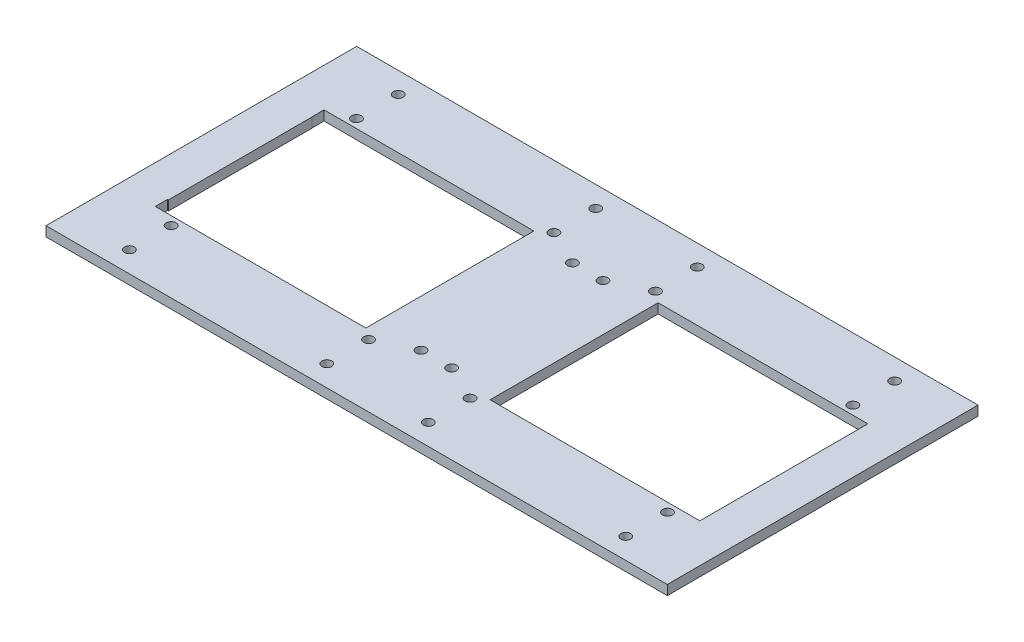
SolidWorks part; units mm, degrees
ref_plane "Front" through (0, 0, 0) normal (0, 0, 1) x (1, 0, 0)
ref_plane "Top" through (0, 0, 0) normal (0, 1, 0) x (1, 0, 0)
ref_plane "Right" through (0, 0, 0) normal (1, 0, 0) x (0, 0, -1)
sketch "Sketch1" plane through (0, 0, 0) normal (0, 1, 0) x (1, 0, 0)
  line L0 (0, -50.8) -> (203.2, -50.8)
  line L1 (0, 0) -> (203.2, 0)
  line L2 (0, 0) -> (0, -101.6)
  line L3 (0, -101.6) -> (203.2, -101.6)
  line L4 (203.2, 0) -> (203.2, -101.6)
  line L5 (101.6, 0) -> (0, 0)
  line L6 (50.8, 0) -> (50.8, -101.6)
  line L7 (101.6, 0) -> (203.2, 0)
  line L8 (152.4, 0) -> (152.4, -101.6)
  line L9 (12.7, -27.3231) -> (12.7, -74.2769)
  line L10 (81.28, -27.3231) -> (81.28, -74.2769)
  line L11 (12.7, -27.3231) -> (81.28, -27.3231)
  line L12 (12.7, -74.2769) -> (81.28, -74.2769)
  line L14 (121.92, -27.3231) -> (121.92, -74.2769)
  line L15 (101.6, 0) -> (101.6, -101.6)
  line L16 (12.7, 0) -> (12.7, -13.6616)
  line L17 (12.7, -13.6616) -> (12.7, -27.3231)
  line L18 (12.7, -74.2769) -> (12.7, -87.9384)
  line L19 (12.7, -87.9384) -> (12.7, -101.6)
  line L20 (190.5, -27.3231) -> (121.92, -27.3231)
  line L22 (190.5, -74.2769) -> (121.92, -74.2769)
  line L23 (190.5, -27.3231) -> (121.92, -27.3231)
  line L24 (106.6, -26.05) -> (96.6, -26.05)
  line L25 (106.6, -26.05) -> (106.6, -75.55)
  line L26 (106.6, -75.55) -> (96.6, -75.55)
  line L27 (96.6, -26.05) -> (96.6, -75.55)
  line L28 (106.6, -26.05) -> (96.6, -75.55) construction
  line L29 (106.6, -75.55) -> (96.6, -26.05) construction
  line L31 (121.92, -27.3231) -> (121.92, -23.3231)
  line L32 (190.5, -23.3231) -> (121.92, -23.3231)
  line L33 (190.5, -74.2769) -> (121.92, -74.2769)
  line L34 (190.5, -74.2769) -> (190.5, -78.2769)
  line L35 (121.92, -74.2769) -> (121.92, -78.2769)
  line L36 (190.5, -78.2769) -> (121.92, -78.2769)
  line L37 (81.28, -74.2769) -> (81.28, -78.2769)
  line L38 (81.28, -74.2769) -> (12.4051, -74.2769)
  line L39 (81.28, -78.2769) -> (12.4051, -78.2769)
  line L40 (12.4051, -74.2769) -> (12.4051, -78.2769)
  line L41 (81.28, -27.3231) -> (81.28, -23.3231)
  line L42 (81.28, -27.3231) -> (12.6484, -27.3231)
  line L43 (81.28, -23.3231) -> (12.6484, -23.3231)
  line L44 (12.6484, -27.3231) -> (12.6484, -23.3231)
  line L45 (118.2, -6.8308) -> (118.2, -20.4924)
  line L46 (190.5, -23.3231) -> (190.5, -27.3231)
  line L47 (190.5, -74.2769) -> (190.5, -27.3231)
  circle A0 centre (12.7, -6.8308) radius 1.6
  circle A1 centre (12.7, -81.1076) radius 1.6
  circle A2 centre (12.7, -94.7692) radius 1.6
  circle A3 centre (12.7, -20.4924) radius 1.6
  circle A4 centre (190.5, -94.7692) radius 1.6
  circle A5 centre (190.5, -81.1076) radius 1.6
  circle A6 centre (190.5, -6.8308) radius 1.6
  circle A7 centre (190.5, -20.4924) radius 1.6
  circle A8 centre (118.2, -6.8308) radius 1.6
  circle A10 centre (118.2, -94.7692) radius 1.6
  circle A12 centre (85, -94.7692) radius 1.6
  circle A15 centre (85, -6.8308) radius 1.6
  circle A16 centre (106.6, -26.05) radius 1.6
  circle A17 centre (96.6, -26.05) radius 1.6
  circle A18 centre (106.6, -75.55) radius 1.6
  circle A19 centre (96.6, -75.55) radius 1.6
  circle A20 centre (118.2, -20.4924) radius 1.6
  circle A21 centre (118.2, -81.1076) radius 1.6
  circle A22 centre (85, -81.1076) radius 1.6
  circle A23 centre (85, -20.4924) radius 1.6
  circle A24 centre (182.769, -6.8308) radius 1.6
  circle A25 centre (182.769, -20.4924) radius 1.6
  circle A26 centre (182.769, -94.7692) radius 1.6
  circle A27 centre (182.769, -81.1076) radius 1.6
  circle A28 centre (20.431, -94.7692) radius 1.6
  circle A29 centre (20.431, -81.1076) radius 1.6
  circle A30 centre (20.431, -20.4924) radius 1.6
  circle A31 centre (20.431, -6.8308) radius 1.6
  point P15 (12.7, -50.8)
  point P16 (12.7, -50.8)
  point P19 (81.28, -50.8)
  point P60 (101.6, -50.8)
  dimension "D5" = 10
  dimension "D7" = 46.9537
  dimension "D1" = 101.6
  dimension "D2" = 203.2
  dimension "D3" = 30.48
  dimension "D4" = 38.1
  dimension "D6" = 49.5
  dimension "D8" = 4
  dimension "D9" = 4
  dimension "D10" = 85
extrude "Boss-Extrude1" add sketch "Sketch1" against normal blind 3.175 contours A3 L17 L11 L6 L5 L16 A0 | A3 L17 L16 A0 L1 L2 L0 L9 | A2 L19 L18 A1 L9 L0 L2 L3 | A2 L19 L3 L6 L12 L18 A1 | L15 L0 L10 L12 L6 L3 | L15 L5 L6 L11 L10 L0 | L20 L8 L1 L15 L0 L14 | L8 L22 L14 L0 L15 L3 | L20 L0 L4 L7 L8 A6 A7 | L22 L8 L3 L4 L0 A4 A5 | A17 L27 L0 L15 L24 | A16 L24 L15 L0 L25 | A19 L26 L15 L0 L27 | A18 L25 L0 L15 L26 | A4 | A6 | A7 | A5 | A2 | A1 | A0 | A3 region at (6.2763, 0, 25.5482) region at (6.2668, 0, 76.0514) region at (32.1315, 0, 11.6058) region at (32.1315, 0, 89.9942) region at (79.5882, 0, 18.393) region at (79.5882, 0, 83.207) region at (99.1301, 0, 38.6182) region at (99.1301, 0, 62.9818) region at (123.6118, 0, 18.393) region at (123.6118, 0, 83.207) region at (104.0699, 0, 38.6182) region at (104.0699, 0, 62.9818) region at (182.0377, 0, 17.5214) region at (182.0377, 0, 84.0786) region at (190.5, 0, 94.7692)
